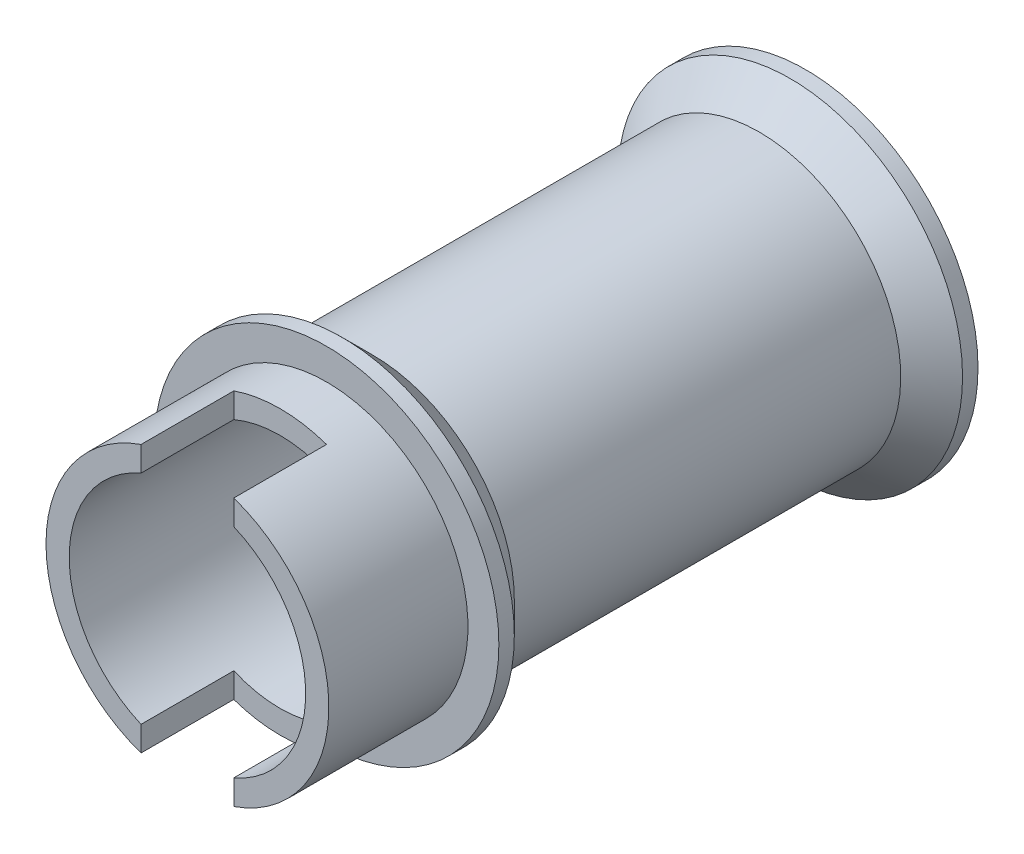
SolidWorks part; units mm, degrees
ref_plane "Top Plane" through (0, 0, 0) normal (0, 0, 1) x (1, 0, 0)
ref_plane "Right Plane" through (0, 0, 0) normal (0, 1, 0) x (1, 0, 0)
ref_plane "Front Plane" through (0, 0, 0) normal (1, 0, 0) x (0, 0, -1)
sketch "Sketch1" plane through (0, 0, 0) normal (0, 0, 1) x (1, 0, 0)
  circle A0 centre (0, 0) radius 7.65
  circle A1 centre (0, 0) radius 9.15
  dimension "D1" = 15.3
  dimension "D2" = 1.5
extrude "Boss-Extrude1" add sketch "Sketch1" along normal blind 40
sketch "Sketch2" plane through (0, 0, 0) normal (0, 1, 0) x (1, 0, 0)
  line L0 (-9.15, -40) -> (9.15, -40) construction
  line L1 (0, -40) -> (0, 0) construction
  line L3 (-3, -40) -> (3, -40)
  line L4 (-3, -40) -> (-3, -34)
  line L5 (-3, -34) -> (3, -34)
  line L6 (3, -40) -> (3, -34)
  point P11 (0, -40)
  dimension "D1" = 6
  dimension "D2" = 6
extrude "Cut-Extrude1" cut sketch "Sketch2" against normal mid plane 30
sketch "Sketch3" plane through (0, 0, 0) normal (0, 1, 0) x (1, 0, 0)
  line L0 (9.15, -40) -> (9.15, 0) construction
  line L1 (9.15, -31) -> (11.15, -31)
  line L2 (9.15, -31) -> (9.15, -28)
  line L3 (9.15, -28) -> (11.15, -28)
  line L4 (11.15, -31) -> (11.15, -28)
  line L6 (9.15, 0) -> (11.15, 0)
  line L7 (9.15, 0) -> (9.15, -3)
  line L8 (9.15, -3) -> (11.15, -3)
  line L9 (11.15, 0) -> (11.15, -3)
  line L11 (9.15, 0) -> (0, 0) construction
  line L12 (9.15, 0) -> (-9.15, 0) construction
  line L13 (0, 0) -> (0, -31) construction
  line L14 (0, -31) -> (9.15, -31) construction
  dimension "D1" = 3
  dimension "D2" = 2
  dimension "D3" = 25
revolve "Revolve1" add sketch "Sketch3" angle 360 about L13
chamfer "Chamfer1" distance 2 angle 45 2 edges at (-11.15, 0, 3) (-11.15, 0, 28)
sketch "Sketch4" plane through (0, 0, 0) normal (0, 0, -1) x (-1, 0, 0)
  line L0 (0, 0) -> (0.6093, -11.1333) construction
  line L1 (-0.6093, -11.1333) -> (0, 0) construction
  line L2 (0, 0) -> (0, -9.15) construction
  line L3 (0.5, -9.1363) -> (0.6093, -11.1333)
  line L4 (-0.6093, -11.1333) -> (-0.5, -9.1363)
  circle A0 centre (0, 0) radius 9.15 construction
  circle A1 centre (0, 0) radius 9.15 construction
  arc A2 (0.5, -9.1363) -> (-0.5, -9.1363) centre (0, 0) cw
  arc A3 (0.6093, -11.1333) -> (-0.6093, -11.1333) centre (0, 0) cw
  circle A4 centre (0, 0) radius 11.15 construction
  point P16 (0, -9.15)
  dimension "D1" = 1
extrude "Cut-Extrude2" cut sketch "Sketch4" against normal blind 5
